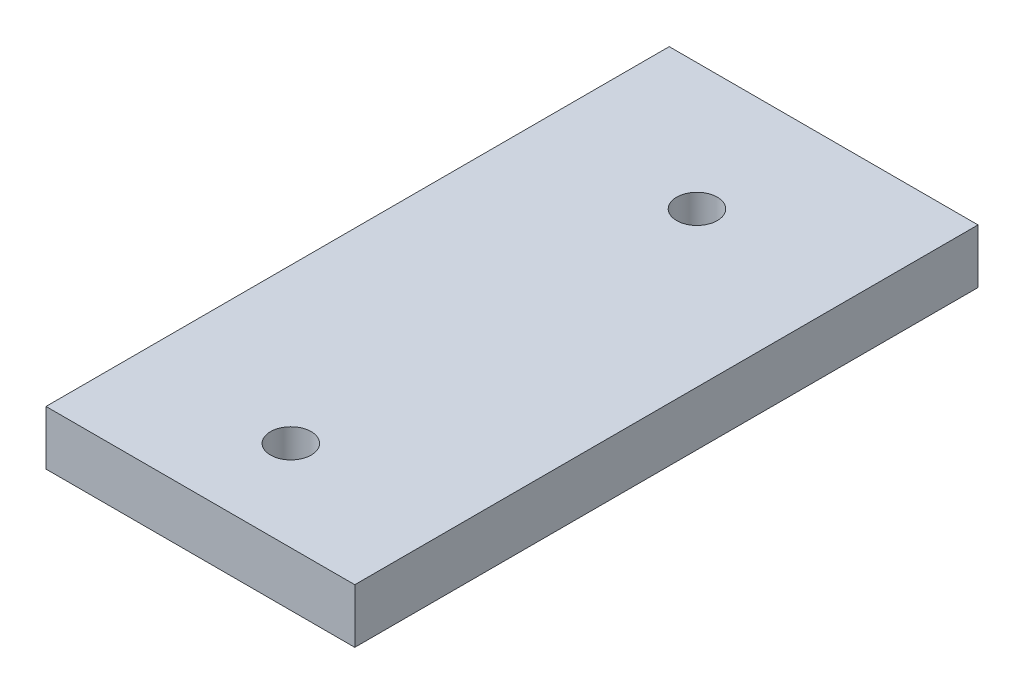
SolidWorks part; units mm, degrees
ref_plane "Front Plane" through (0, 0, 0) normal (0, 0, 1) x (1, 0, 0)
ref_plane "Top Plane" through (0, 0, 0) normal (0, 1, 0) x (1, 0, 0)
ref_plane "Right Plane" through (0, 0, 0) normal (1, 0, 0) x (0, 0, -1)
sketch "Sketch1" plane through (0, 0, 0) normal (0, 1, 0) x (1, 0, 0)
  line L9 (-14.7858, -27.8964) -> (19.3496, -27.8964)
  line L10 (-14.7858, -27.8964) -> (-14.7858, 40.9996)
  line L11 (-14.7858, 40.9996) -> (19.3496, 40.9996)
  line L12 (19.3496, -27.8964) -> (19.3496, 40.9996)
extrude "Boss-Extrude1" add sketch "Sketch1" along normal blind 6
sketch "Sketch2" plane through (0, 6, 0) normal (0, 1, 0) x (1, 0, 0)
  line L0 (19.3496, -17.8964) -> (-14.7858, -17.8964) construction
  line L1 (19.3496, -27.8964) -> (19.3496, 40.9996) construction
  line L2 (-14.7858, 40.9996) -> (-14.7858, -27.8964) construction
  line L3 (-14.7858, -27.8964) -> (19.3496, -27.8964) construction
  line L4 (-14.7858, 26.9996) -> (19.3496, 26.9996) construction
  line L5 (19.3496, 40.9996) -> (-14.7858, 40.9996) construction
  line L6 (2.2819, 40.9996) -> (2.2819, -27.8964) construction
  circle A0 centre (2.2819, -17.8964) radius 2.25
  circle A1 centre (2.2819, 26.9996) radius 2.25
  point P18 (1.704, -27.7878)
  point P19 (1.704, 41.1082)
  dimension "D3" = 4.5
  dimension "D4" = 4.5
  dimension "D1" = 10
  dimension "D2" = 14
extrude "Cut-Extrude1" cut sketch "Sketch2" against normal up to next
